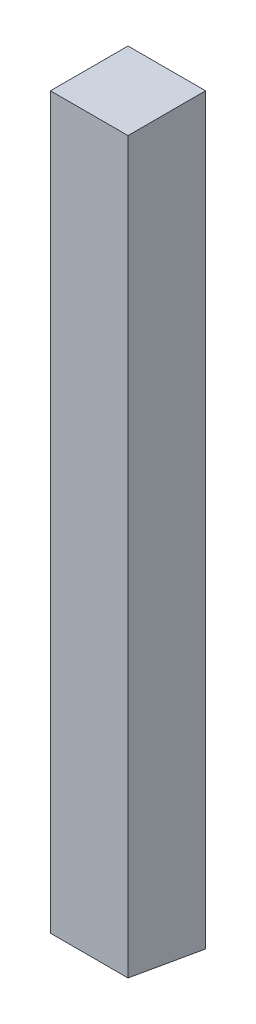
SolidWorks part; units mm, degrees
material "Pine"
ref_plane "Front Plane" through (0, 0, 0) normal (0, 0, 1) x (1, 0, 0)
ref_plane "Top Plane" through (0, 0, 0) normal (0, 1, 0) x (1, 0, 0)
ref_plane "Right Plane" through (0, 0, 0) normal (1, 0, 0) x (0, 0, -1)
sketch "Sketch1" plane through (0, 0, 0) normal (0, 1, 0) x (1, 0, 0)
  line L1 (-19.05, 19.05) -> (19.05, 19.05)
  line L2 (-19.05, 19.05) -> (-19.05, -19.05)
  line L4 (19.05, 19.05) -> (19.05, -19.05)
  line L5 (-19.05, 19.05) -> (19.05, -19.05) construction
  line L6 (-19.05, -19.05) -> (19.05, 19.05) construction
  line L7 (-19.05, -19.05) -> (19.05, -19.05)
  point P0 (0, 0)
  dimension "D1" = 38.1
  dimension "D2" = 38.1
extrude "Boss-Extrude1" add sketch "Sketch1" along normal blind 365
sketch "Sketch2" plane through (-19.05, 0, 0) normal (-1, 0, 0) x (0, 0, 1)
  line L0 (-19.05, 0) -> (19.05, 6.7181)
  line L1 (19.05, 365) -> (19.05, 0) construction
  line L2 (19.05, 6.7181) -> (19.05, 0)
  line L3 (19.05, 0) -> (-19.05, 0)
  dimension "D1" = 10
extrude "Cut-Extrude1" cut sketch "Sketch2" against normal up to next
